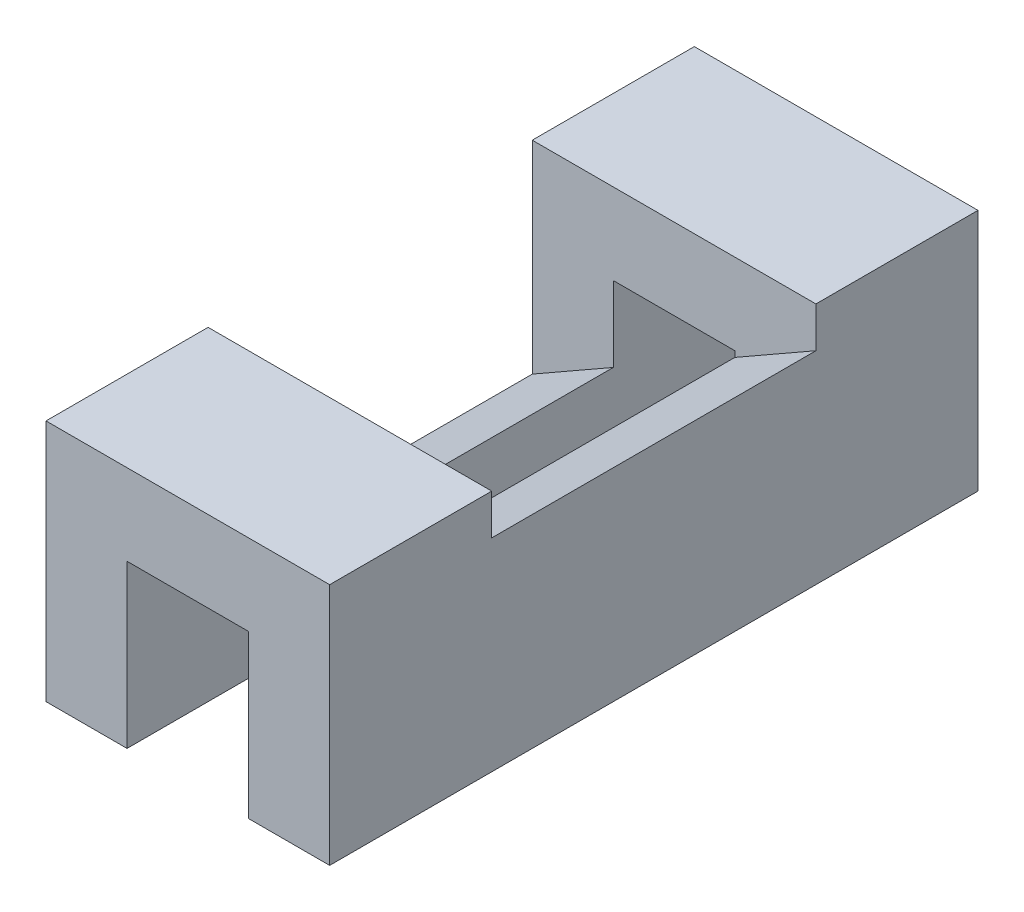
SolidWorks part; units mm, degrees
ref_plane "Front Plane" through (0, 0, 0) normal (0, 0, 1) x (1, 0, 0)
ref_plane "Top Plane" through (0, 0, 0) normal (0, 1, 0) x (1, 0, 0)
ref_plane "Right Plane" through (0, 0, 0) normal (1, 0, 0) x (0, 0, -1)
sketch "Sketch1" plane through (0, 0, 0) normal (0, 0, 1) x (1, 0, 0)
  line L0 (-35, 0) -> (-25, 0)
  line L1 (-25, 0) -> (-25, 20)
  line L2 (-25, 20) -> (-10, 20)
  line L3 (-10, 20) -> (-10, 0)
  line L4 (-10, 0) -> (0, 0)
  line L5 (0, 0) -> (0, 30)
  line L6 (0, 30) -> (-35, 30)
  line L7 (-35, 30) -> (-35, 0)
  point P8 (0, 0)
  dimension "D1" = 10
  dimension "D2" = 15
  dimension "D3" = 35
  dimension "D4" = 20
  dimension "D5" = 30
extrude "Boss-Extrude1" add sketch "Sketch1" along normal blind 80
sketch "Sketch2" plane through (0, 0, 80) normal (0, 0, 1) x (1, 0, 0)
  line L1 (-35, 30) -> (-35, 0) construction
  line L2 (0, 0) -> (0, 30) construction
  line L3 (0, 25) -> (0, 30)
  line L4 (0, 30) -> (-35, 30)
  line L5 (-35, 30) -> (-35, 5)
  line L6 (-25, 10.7143) -> (-25, 20)
  line L7 (-25, 0) -> (-25, 20) construction
  line L8 (-25, 20) -> (-10, 20)
  line L9 (-10, 20) -> (-10, 19.2857)
  line L10 (-25, 10.7143) -> (-35, 5)
  line L11 (-10, 19.2857) -> (0, 25)
  dimension "D1" = 5
  dimension "D2" = 5
extrude "Cut-Extrude1" cut sketch "Sketch2" against normal blind 60
extrude "Boss-Extrude2" add sketch "Sketch2<2>" against normal blind 20
sketch "Sketch2<2>" plane through (0, 0, 80) normal (0, 0, 1) x (1, 0, 0) same geometry as "Sketch2"
